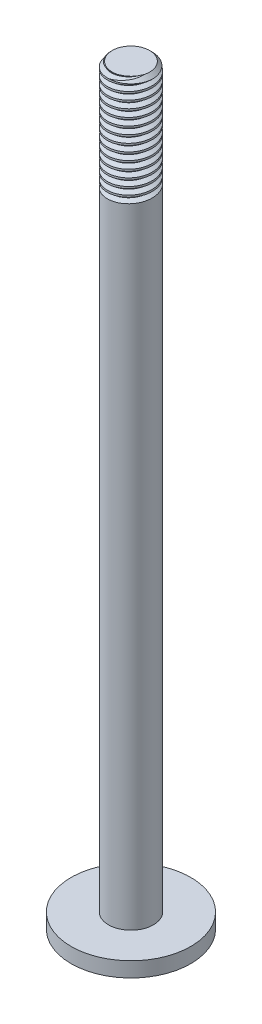
SolidWorks part; units mm, degrees
material "6063-T5"
ref_plane "Plano frontal" through (0, 0, 0) normal (0, 0, 1) x (1, 0, 0)
ref_plane "Plano superior" through (0, 0, 0) normal (0, 1, 0) x (1, 0, 0)
ref_plane "Plano direito" through (0, 0, 0) normal (1, 0, 0) x (0, 0, -1)
sketch "Esboço1" plane through (0, 0, 0) normal (0, 1, 0) x (1, 0, 0)
  circle A0 centre (0, 0) radius 8
  dimension "D1" = 16
extrude "Ressalto-extrusão1" add sketch "Esboço1" along normal blind 2
sketch "Esboço2" plane through (0, 2, 0) normal (0, 1, 0) x (1, 0, 0)
  circle A0 centre (0, 0) radius 3
  dimension "D1" = 6
extrude "Ressalto-extrusão2" add sketch "Esboço2" along normal blind 98.5
chamfer "Chanfro1" distance 0.5 angle 45 1 edges at (0, 100.5, 3)
thread "Rosca1" pitch 1 method cut trim with start face yes profile "Perfil da rosca1" start angle 0, offset 1, length 15, pitch 1, diameter 6
ref_plane "Plano1" through (-3, 101.5, 0) normal (0, 0, -1) x (1, 0, 0)
sketch "Perfil da rosca1" plane through (-3, 101.5, 0) normal (0, 0, -1) x (1, 0, 0)
  line L0 (0, 0) -> (0, 1) construction
  line L1 (0, 0) -> (0.5413, 0.3125)
  line L2 (0.5413, 0.3125) -> (0.5413, 0.4375)
  line L3 (0.5413, 0.4375) -> (0, 0.75)
  line L4 (0.5413, 0.375) -> (0, 0.375) construction
  line L11 (0, 0) -> (0, 0.75)
  point P2 (0, 0)
  dimension "Pitch" = 1
  dimension "Profile_Angle" = 60
  dimension "Profile_Land" = 0.125
  dimension "Profile_Height" = 0.5413
